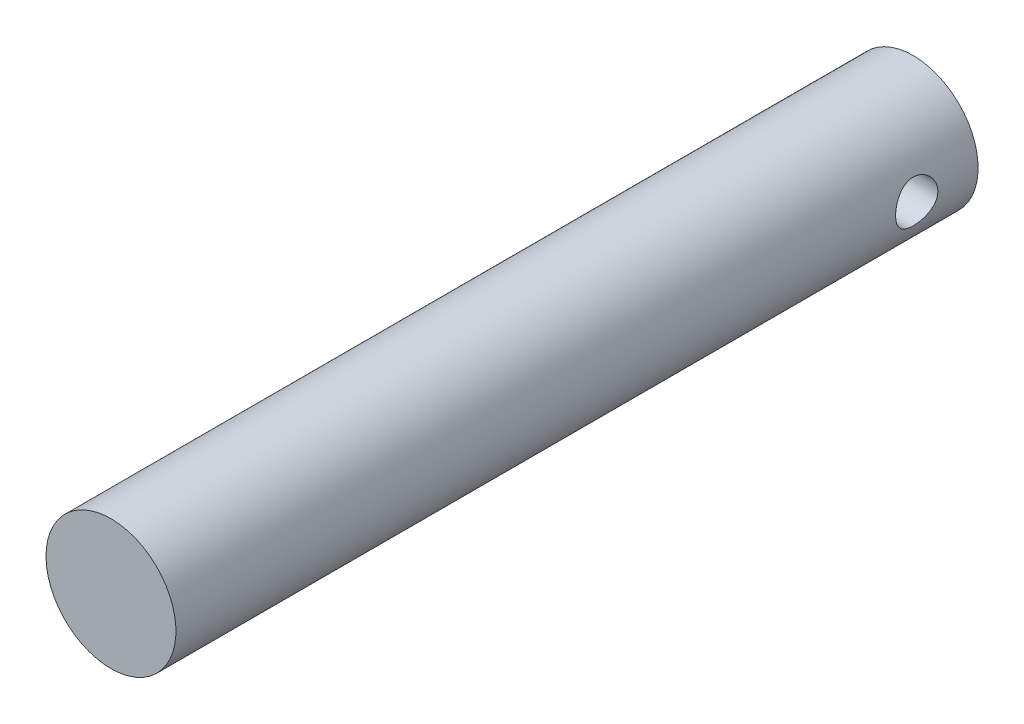
SolidWorks part; units mm, degrees
ref_plane "Front Plane" through (0, 0, 0) normal (0, 0, 1) x (1, 0, 0)
ref_plane "Top Plane" through (0, 0, 0) normal (0, 1, 0) x (1, 0, 0)
ref_plane "Right Plane" through (0, 0, 0) normal (1, 0, 0) x (0, 0, -1)
sketch "Sketch1" plane through (0, 0, 0) normal (0, 0, 1) x (1, 0, 0)
  line L1 (-22.9358, 25.4587) -> (27.0642, 25.4587)
  line L2 (-22.9358, 25.4587) -> (-22.9358, -24.5413)
  line L3 (-22.9358, -24.5413) -> (27.0642, -24.5413)
  line L4 (27.0642, 25.4587) -> (27.0642, -24.5413)
  dimension "D1" = 50
  dimension "D2" = 50
extrude "Boss-Extrude1" add sketch "Sketch1" along normal blind 123.5
sketch "Sketch2" plane through (-22.9358, 0, 0) normal (-1, 0, 0) x (0, 0, 1)
  line L0 (0, 25.4587) -> (0, -24.5413) construction
  line L1 (123.5, 25.4587) -> (0, 25.4587) construction
  circle A0 centre (9.45, 0.4587) radius 3.25
  dimension "D1" = 6.5
  dimension "D2" = 9.45
  dimension "D3" = 25
extrude "Cut-Extrude1" cut sketch "Sketch2" against normal blind 50
sketch "Sketch3" plane through (0, 0, 0) normal (0, 0, -1) x (-1, 0, 0)
  line L0 (-27.0642, -24.5413) -> (-27.0642, 25.4587) construction
  line L1 (-27.0642, 25.4587) -> (22.9358, 25.4587) construction
  circle A0 centre (-2.0642, 0.4587) radius 10
  point P6 (-2.0813, 5.4341)
  point P7 (0, 0)
  dimension "D3" = 20
  dimension "D1" = 25
  dimension "D2" = 25
extrude "Cut-Extrude2" cut sketch "Sketch3" against normal blind 123.5 flip side to cut
ref_axis "Axis1" through (12.0642, 0.4587, 9.45) along (-1, 0, 0)
